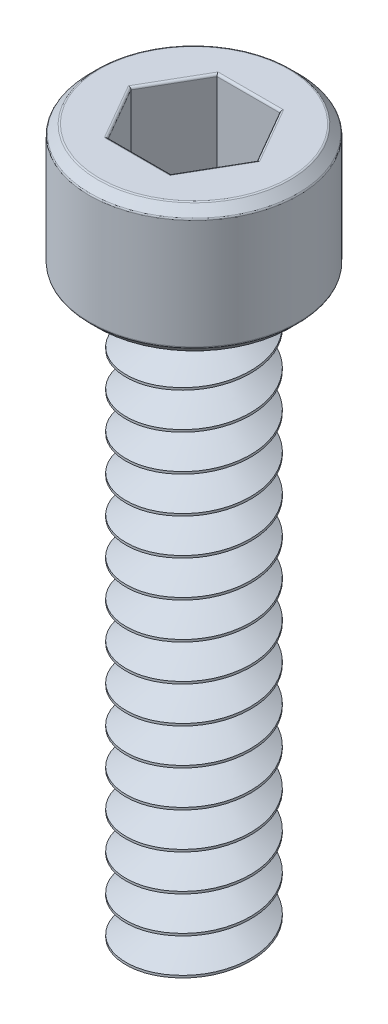
SolidWorks part; units mm, degrees
ref_plane "Front Plane" through (0, 0, 0) normal (0, 0, 1) x (1, 0, 0)
ref_plane "Top Plane" through (0, 0, 0) normal (0, 1, 0) x (1, 0, 0)
ref_plane "Right Plane" through (0, 0, 0) normal (1, 0, 0) x (0, 0, -1)
sketch "Sketch1" plane through (0, 0, 0) normal (0, 0, 1) x (1, 0, 0)
  line L0 (0, 0) -> (0, 9.3591) construction
  line L1 (0, 15.55) -> (2.1, 15.55)
  line L2 (2.3, 15.35) -> (2.3, 12.9)
  line L3 (2.1, 12.7) -> (1.375, 12.7)
  line L4 (1.375, 12.7) -> (1.375, 0)
  line L5 (1.375, 0) -> (0, 0)
  line L6 (0, 0) -> (0, 15.55)
  line L7 (2.1, 15.55) -> (2.3, 15.35)
  line L8 (2.3, 12.9) -> (2.1, 12.7)
  point P4 (2.3, 15.55)
  point P7 (2.3, 12.7)
  dimension "D1" = 4.6
  dimension "D2" = 2.85
  dimension "D3" = 2.75
  dimension "D4" = 12.7
revolve "Revolve1" add sketch "Sketch1" angle 360 about L0
sketch "Sketch2" plane through (0, 15.55, 0) normal (0, 1, 0) x (1, 0, 0)
  line L1 (1.3856, 0) -> (0.6928, 1.2)
  line L2 (0.6928, 1.2) -> (-0.6928, 1.2)
  line L3 (-0.6928, 1.2) -> (-1.3856, 0)
  line L4 (-1.3856, 0) -> (-0.6928, -1.2)
  line L5 (-0.6928, -1.2) -> (0.6928, -1.2)
  line L6 (0.6928, -1.2) -> (1.3856, 0)
  circle A0 centre (0, 0) radius 1.2 construction
  dimension "D1" = 2.4
extrude "Cut-Extrude1" cut sketch "Sketch2" against normal blind 2
sketch "Sketch4" plane through (0, 0, 0) normal (0, -1, 0) x (1, 0, 0)
  circle A0 centre (0, 0) radius 1.375
  circle A1 centre (0, 0) radius 1.375 construction
curve "Helix/Spiral1" pitch 0.8 height 13 turns 16.25
sketch "Sketch5" plane through (0, 0, 0) normal (0, 0, 1) x (1, 0, 0)
  line L0 (-1.375, 0) -> (-0.7255, 0.375)
  line L1 (-0.7255, 0.375) -> (-1.375, 0.75)
  line L2 (-1.375, 12.7) -> (-1.375, 0) construction
  line L3 (-1.375, 0.75) -> (-1.375, 0)
  dimension "D1" = 0.75
  dimension "D2" = 60
sweep "Cut-Sweep2" cut profiles "Sketch5" path "Helix/Spiral1" align with end faces yes
fillet "Fillet1" radius 0.05 10 edges at (0, 12.9, -2.3) (0, 12.7, -2.1) (0, 15.35, -2.3) (0, 15.55, -2.1) (0, 15.55, 1.2) (1.0392, 15.55, 0.6) (1.0392, 15.55, -0.6) (0, 15.55, -1.2) (-1.0392, 15.55, -0.6) (-1.0392, 15.55, 0.6)
